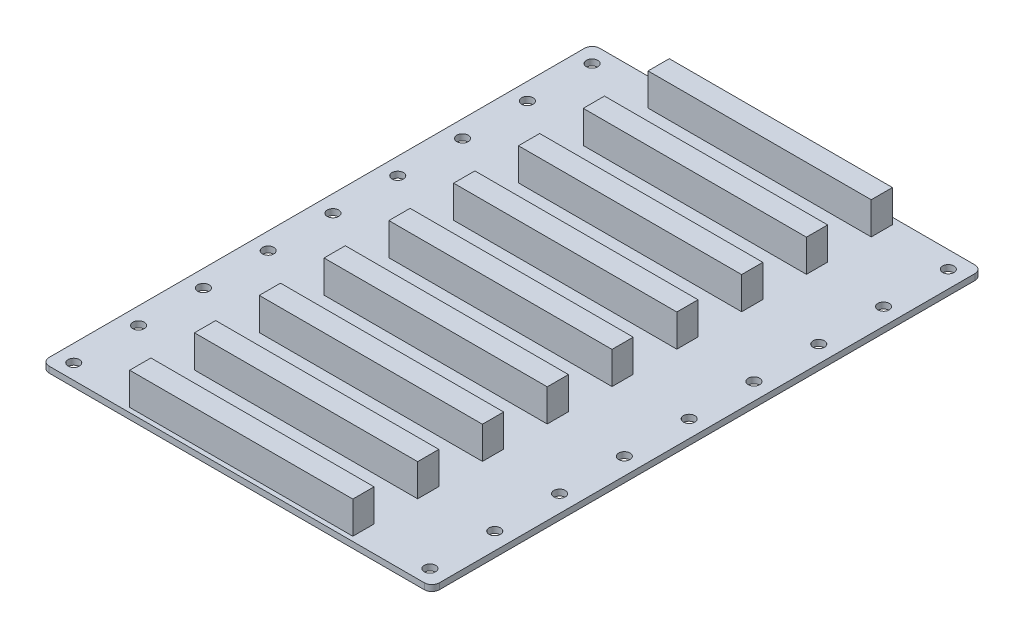
SolidWorks part; units mm, degrees
ref_plane "Front Plane" through (0, 0, 0) normal (0, 0, 1) x (1, 0, 0)
ref_plane "Top Plane" through (0, 0, 0) normal (0, 1, 0) x (1, 0, 0)
ref_plane "Right Plane" through (0, 0, 0) normal (1, 0, 0) x (0, 0, -1)
sketch "Sketch1" plane through (0, 0, 0) normal (0, 1, 0) x (1, 0, 0)
  line L1 (-51.5, -72.65) -> (51.5, -72.65)
  line L2 (-51.5, -72.65) -> (-51.5, 72.65)
  line L3 (-51.5, 72.65) -> (51.5, 72.65)
  line L4 (51.5, -72.65) -> (51.5, 72.65)
  line L5 (-51.5, -72.65) -> (51.5, 72.65) construction
  line L6 (-51.5, 72.65) -> (51.5, -72.65) construction
  point P0 (0, 0)
  dimension "D1" = 103
  dimension "D2" = 145.3
extrude "Boss-Extrude1" add sketch "Sketch1" along normal blind 1.6
sketch "Sketch3" plane through (0, 1.6, 0) normal (0, 1, 0) x (1, 0, 0)
  line L0 (0, 72.65) -> (0, -72.65) construction
  line L1 (51.5, 72.65) -> (-51.5, 72.65) construction
  line L2 (-51.5, -72.65) -> (51.5, -72.65) construction
  line L4 (-51.5, 72.65) -> (-51.5, -72.65) construction
  circle A1 centre (-47, -68.65) radius 1.5
  circle A3 centre (-47, -51.55) radius 1.5
  circle A4 centre (-47, -34.45) radius 1.5
  circle A5 centre (-47, -17.35) radius 1.5
  circle A6 centre (-47, -0.25) radius 1.5
  circle A7 centre (-47, 16.85) radius 1.5
  circle A8 centre (-47, 33.95) radius 1.5
  circle A9 centre (-47, 51.05) radius 1.5
  circle A10 centre (-47, 68.15) radius 1.5
  circle A11 centre (47, 68.15) radius 1.5
  circle A12 centre (47, 51.05) radius 1.5
  circle A13 centre (47, 33.95) radius 1.5
  circle A14 centre (47, 16.85) radius 1.5
  circle A15 centre (47, -0.25) radius 1.5
  circle A16 centre (47, -17.35) radius 1.5
  circle A17 centre (47, -34.45) radius 1.5
  circle A18 centre (47, -51.55) radius 1.5
  circle A19 centre (47, -68.65) radius 1.5
  dimension "D1" = 3
  dimension "D2" = 4.5
  dimension "D3" = 9
  dimension "D4" = 17.1
  dimension "D5" = 4
extrude "Cut-Extrude2" cut sketch "Sketch3" against normal up to surface (1.6 mm away) up to face at (0, 0, 0)
sketch "Sketch4" plane through (0, 1.6, 0) normal (0, 1, 0) x (1, 0, 0)
  line L0 (-29.445, -54.35) -> (-29.445, -48.75)
  line L1 (-29.445, -71.45) -> (29.445, -71.45)
  line L2 (-29.445, -71.45) -> (-29.445, -65.85)
  line L3 (-29.445, -65.85) -> (29.445, -65.85)
  line L4 (29.445, -71.45) -> (29.445, -65.85)
  line L5 (-29.445, -71.45) -> (29.445, -65.85) construction
  line L6 (-29.445, -65.85) -> (29.445, -71.45) construction
  line L7 (-51.5, -72.65) -> (51.5, -72.65) construction
  line L8 (51.5, -72.65) -> (51.5, 72.65) construction
  line L9 (-29.445, -54.35) -> (29.445, -54.35)
  line L10 (29.445, -54.35) -> (29.445, -48.75)
  line L11 (-29.445, -48.75) -> (29.445, -48.75)
  line L12 (-29.445, -37.25) -> (-29.445, -31.65)
  line L13 (-29.445, -37.25) -> (29.445, -37.25)
  line L14 (29.445, -37.25) -> (29.445, -31.65)
  line L15 (-29.445, -31.65) -> (29.445, -31.65)
  line L16 (-29.445, -20.15) -> (-29.445, -14.55)
  line L17 (-29.445, -20.15) -> (29.445, -20.15)
  line L18 (29.445, -20.15) -> (29.445, -14.55)
  line L19 (-29.445, -14.55) -> (29.445, -14.55)
  line L20 (-29.445, -3.05) -> (-29.445, 2.55)
  line L21 (-29.445, -3.05) -> (29.445, -3.05)
  line L22 (29.445, -3.05) -> (29.445, 2.55)
  line L23 (-29.445, 2.55) -> (29.445, 2.55)
  line L24 (-29.445, 14.05) -> (-29.445, 19.65)
  line L25 (-29.445, 14.05) -> (29.445, 14.05)
  line L26 (29.445, 14.05) -> (29.445, 19.65)
  line L27 (-29.445, 19.65) -> (29.445, 19.65)
  line L28 (-29.445, 31.15) -> (-29.445, 36.75)
  line L29 (-29.445, 31.15) -> (29.445, 31.15)
  line L30 (29.445, 31.15) -> (29.445, 36.75)
  line L31 (-29.445, 36.75) -> (29.445, 36.75)
  line L32 (-29.445, 48.25) -> (-29.445, 53.85)
  line L33 (-29.445, 48.25) -> (29.445, 48.25)
  line L34 (29.445, 48.25) -> (29.445, 53.85)
  line L35 (-29.445, 53.85) -> (29.445, 53.85)
  line L36 (-29.445, 65.35) -> (-29.445, 70.95)
  line L37 (-29.445, 65.35) -> (29.445, 65.35)
  line L38 (29.445, 65.35) -> (29.445, 70.95)
  line L39 (-29.445, 70.95) -> (29.445, 70.95)
  point P0 (0, -68.65)
  dimension "D1" = 5.6
  dimension "D2" = 58.89
  dimension "D3" = 4
  dimension "D4" = 51.5
  dimension "D6" = 11.5
  dimension "D5" = 9
extrude "Boss-Extrude2" add sketch "Sketch4" along normal blind 8.5
fillet "Fillet2" radius 2 4 edges at (-51.5, 0.8, -72.65) (51.5, 0.8, -72.65) (51.5, 0.8, 72.65) (-51.5, 0.8, 72.65)
